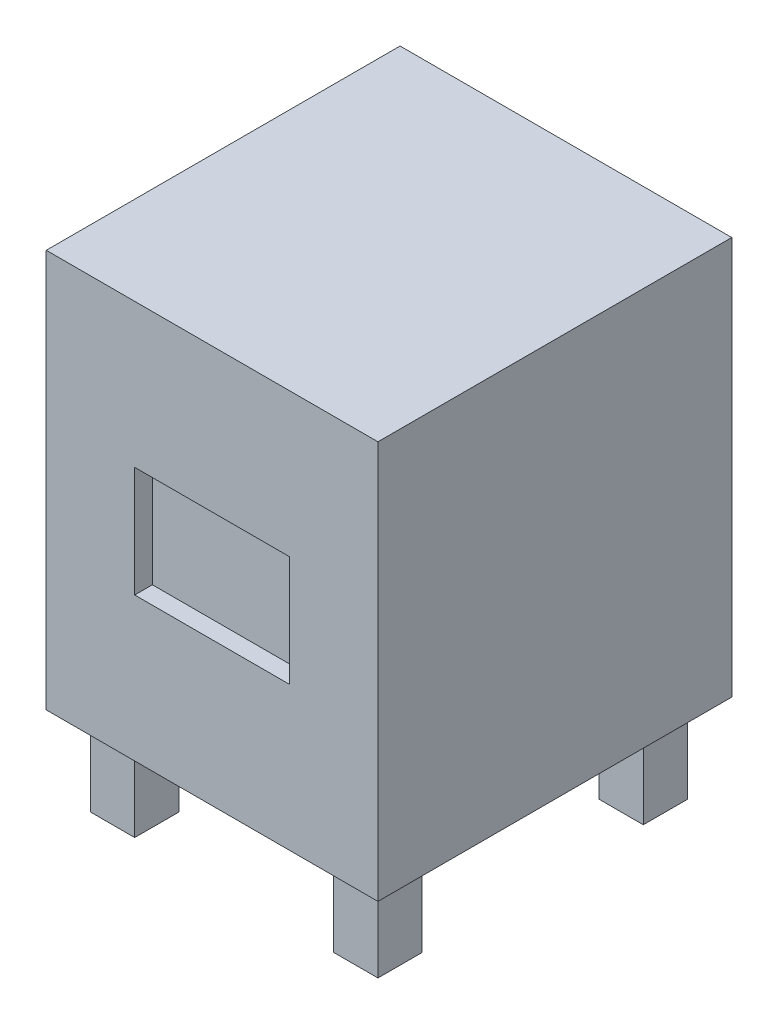
SolidWorks part; units mm, degrees
ref_plane "Front Plane" through (0, 0, 0) normal (0, 0, 1) x (1, 0, 0)
ref_plane "Top Plane" through (0, 0, 0) normal (0, 1, 0) x (1, 0, 0)
ref_plane "Right Plane" through (0, 0, 0) normal (1, 0, 0) x (0, 0, -1)
sketch "Sketch1" plane through (0, 0, 0) normal (0, 0, 1) x (1, 0, 0)
  line L1 (-47.625, -57.15) -> (47.625, -57.15)
  line L2 (-47.625, -57.15) -> (-47.625, 57.15)
  line L3 (-47.625, 57.15) -> (47.625, 57.15)
  line L4 (47.625, -57.15) -> (47.625, 57.15)
  line L5 (-47.625, -57.15) -> (47.625, 57.15) construction
  line L6 (-47.625, 57.15) -> (47.625, -57.15) construction
  line L11 (-13.2292, -15.875) -> (13.2292, 15.875) construction
  line L12 (-13.2292, 15.875) -> (13.2292, -15.875) construction
  point P0 (0, 0)
  point P6 (0, 0)
  dimension "D1" = 114.3
  dimension "D2" = 95.25
extrude "Boss-Extrude1" add sketch "Sketch1" along normal blind 101.6
sketch "Sketch2" plane through (0, 0, 101.6) normal (0, 0, 1) x (1, 0, 0)
  line L1 (-22.225, -15.875) -> (22.225, -15.875)
  line L2 (-22.225, -15.875) -> (-22.225, 15.875)
  line L3 (-22.225, 15.875) -> (22.225, 15.875)
  line L4 (22.225, -15.875) -> (22.225, 15.875)
  line L5 (-22.225, -15.875) -> (22.225, 15.875) construction
  line L6 (-22.225, 15.875) -> (22.225, -15.875) construction
  point P0 (0, 0)
  dimension "D1" = 31.75
  dimension "D2" = 44.45
extrude "Cut-Extrude1" cut sketch "Sketch2" against normal blind 5.08
sketch "Sketch3" plane through (0, -57.15, 0) normal (0, -1, 0) x (1, 0, 0)
  line L0 (0, 101.6) -> (0, 0) construction
  line L1 (-47.625, 101.6) -> (47.625, 101.6) construction
  line L2 (-47.625, 0) -> (47.625, 0) construction
  line L3 (-34.925, 101.6) -> (-34.925, 88.9) construction
  line L4 (-34.925, 88.9) -> (-47.625, 88.9) construction
  line L5 (-47.625, 101.6) -> (-47.625, 0) construction
  line L6 (-47.625, 50.8) -> (47.625, 50.8) construction
  line L7 (-41.275, 82.55) -> (-28.575, 82.55)
  line L8 (-41.275, 82.55) -> (-41.275, 95.25)
  line L9 (-41.275, 95.25) -> (-28.575, 95.25)
  line L10 (-28.575, 82.55) -> (-28.575, 95.25)
  line L11 (-41.275, 82.55) -> (-28.575, 95.25) construction
  line L12 (-41.275, 95.25) -> (-28.575, 82.55) construction
  line L13 (47.625, 101.6) -> (47.625, 0) construction
  line L14 (-41.275, 6.35) -> (-28.575, 19.05) construction
  line L15 (-41.275, 19.05) -> (-28.575, 6.35) construction
  line L16 (-34.925, 12.7) -> (-47.625, 12.7) construction
  line L17 (-34.925, 0) -> (-34.925, 12.7) construction
  line L18 (-28.575, 19.05) -> (-28.575, 6.35)
  line L19 (-41.275, 6.35) -> (-28.575, 6.35)
  line L20 (-41.275, 19.05) -> (-41.275, 6.35)
  line L21 (-41.275, 19.05) -> (-28.575, 19.05)
  line L22 (41.275, 95.25) -> (28.575, 82.55) construction
  line L23 (41.275, 82.55) -> (28.575, 95.25) construction
  line L24 (34.925, 88.9) -> (47.625, 88.9) construction
  line L25 (34.925, 101.6) -> (34.925, 88.9) construction
  line L26 (28.575, 82.55) -> (28.575, 95.25)
  line L27 (41.275, 95.25) -> (28.575, 95.25)
  line L28 (41.275, 82.55) -> (41.275, 95.25)
  line L29 (41.275, 82.55) -> (28.575, 82.55)
  line L30 (34.925, 0) -> (34.925, 12.7) construction
  line L31 (34.925, 12.7) -> (47.625, 12.7) construction
  line L32 (41.275, 19.05) -> (28.575, 6.35) construction
  line L33 (41.275, 6.35) -> (28.575, 19.05) construction
  line L34 (41.275, 19.05) -> (28.575, 19.05)
  line L35 (41.275, 19.05) -> (41.275, 6.35)
  line L36 (41.275, 6.35) -> (28.575, 6.35)
  line L37 (28.575, 19.05) -> (28.575, 6.35)
  dimension "D1" = 12.7
  dimension "D2" = 12.7
  dimension "D3" = 12.7
  dimension "D4" = 12.7
extrude "Boss-Extrude2" add sketch "Sketch3" along normal blind 25.4
sketch "Sketch4" plane through (47.625, 0, 0) normal (1, 0, 0) x (0, 0, -1)
  line L0 (-50.8, -57.15) -> (-50.8, 57.15) construction
  line L1 (-101.6, 57.15) -> (0, 57.15) construction
  line L2 (-101.6, -57.15) -> (0, -57.15) construction
  line L5 (-67.945, -8.636) -> (-33.655, -8.636)
  line L6 (-67.945, -8.636) -> (-67.945, 8.636)
  line L7 (-67.945, 8.636) -> (-33.655, 8.636)
  line L8 (-33.655, -8.636) -> (-33.655, 8.636)
  line L9 (-67.945, -8.636) -> (-33.655, 8.636) construction
  line L10 (-67.945, 8.636) -> (-33.655, -8.636) construction
  point P6 (-50.8, 0)
  dimension "D1" = 17.272
  dimension "D2" = 34.29
sketch "Sketch6" plane through (0, 0, 0) normal (0, 0, -1) x (-1, 0, 0)
  line L1 (-17.145, -8.636) -> (17.145, -8.636)
  line L2 (-17.145, -8.636) -> (-17.145, 8.636)
  line L3 (-17.145, 8.636) -> (17.145, 8.636)
  line L4 (17.145, -8.636) -> (17.145, 8.636)
  line L5 (-17.145, -8.636) -> (17.145, 8.636) construction
  line L6 (-17.145, 8.636) -> (17.145, -8.636) construction
  point P0 (0, 0)
  dimension "D1" = 17.272
  dimension "D2" = 34.29
hole_wizard "#4-40 Tapped Hole2" positions "3DSketch2" profile "Sketch7" tap size "#4-40" standard "Ansi Inch"
sketch3d "3DSketch2"
  point P0 (17.145, 8.636, 0)
  point P3 (-17.145, 8.636, 0)
  point P6 (-17.145, -8.636, 0)
  point P9 (17.145, -8.636, 0)
sketch "Sketch7" plane through (17.145, 8.636, 0) normal (1, 0, 0) x (0, 1, 0)
  line L0 (0, 0) -> (0, 8.2792)
  line L1 (0, 8.2792) -> (1.1303, 7.6)
  line L2 (1.1303, 7.6) -> (1.1303, 0)
  line L5 (1.1303, 0) -> (0, 0)
  line L10 (0, 8.2792) -> (-1.1303, 7.6) construction
  line L11 (0, -6.35) -> (0, 107.95) construction
  dimension "Tap Drill Dia." = 2.2606
  dimension "Tap Drill Depth" = 7.6
  dimension "Drill Angle" = 118
cosmetic thread "Hole Thread5" parameters "D1"=5.69, "D2"=2.8448
cosmetic thread "Hole Thread6" parameters "D1"=5.69, "D2"=2.8448
cosmetic thread "Hole Thread7" parameters "D1"=5.69, "D2"=2.8448
cosmetic thread "Hole Thread8" parameters "D1"=5.69, "D2"=2.8448
